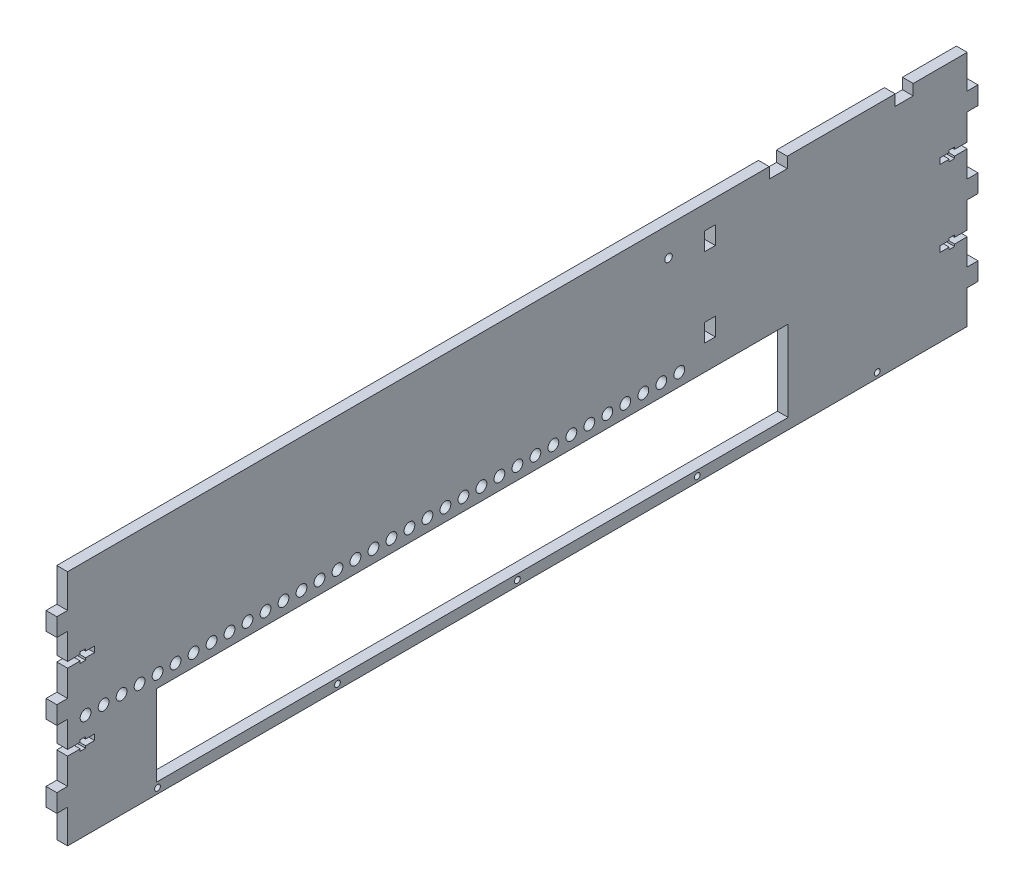
SolidWorks part; units mm, degrees
ref_plane "Front Plane" through (0, 0, 0) normal (0, 0, 1) x (1, 0, 0)
ref_plane "Top Plane" through (0, 0, 0) normal (0, 1, 0) x (1, 0, 0)
ref_plane "Right Plane" through (0, 0, 0) normal (1, 0, 0) x (0, 0, -1)
sketch "Sketch1" plane through (0, 0, 0) normal (1, 0, 0) x (0, 0, -1)
  line L1 (-250, -66) -> (250, -66)
  line L2 (-250, -66) -> (-250, 66)
  line L3 (-250, 66) -> (250, 66)
  line L4 (250, -66) -> (250, 66)
  line L5 (-250, -66) -> (250, 66) construction
  line L6 (-250, 66) -> (250, -66) construction
  point P0 (0, 0)
  dimension "D1" = 132
  dimension "D2" = 500
extrude "Boss-Extrude1" add sketch "Sketch1" along normal blind 6
sketch "Sketch4" plane through (0, 0, 250) normal (0, 0, 1) x (1, 0, 0)
  line L0 (0, 66) -> (0, -66) construction
  line L1 (0, 47.3321) -> (6, 47.3321)
  line L2 (0, 47.3321) -> (0, 37.3321)
  line L3 (0, 37.3321) -> (6, 37.3321)
  line L4 (6, 47.3321) -> (6, 37.3321)
  line L5 (6, 66) -> (6, -66) construction
  line L6 (0, 37.3321) -> (6, 37.3321) construction
  line L7 (0, -66) -> (0, 66) construction
  line L8 (6, 47.3321) -> (0, 47.3321) construction
  line L9 (0, -5) -> (6, -5) construction
  line L10 (0, -5) -> (6, -5)
  line L11 (0, -5) -> (0, 5)
  line L12 (0, 5) -> (6, 5)
  line L13 (6, -5) -> (6, 5)
  line L14 (6, -66) -> (6, 66) construction
  line L15 (6, 5) -> (0, 5) construction
  line L16 (6, -37.3321) -> (0, -37.3321) construction
  line L17 (0, -47.3321) -> (6, -47.3321)
  line L18 (0, -47.3321) -> (0, -37.3321)
  line L19 (0, -37.3321) -> (6, -37.3321)
  line L20 (6, -47.3321) -> (6, -37.3321)
  line L21 (0, -47.3321) -> (6, -47.3321) construction
extrude "Boss-Extrude2" add sketch "Sketch4" along normal blind 6
sketch "Sketch5" plane through (0, 0, 0) normal (-1, 0, 0) x (0, 0, 1)
  line L0 (250, 37.3321) -> (250, 5) construction
  line L1 (250, 5) -> (250, -5) construction
  line L2 (250, -5) -> (250, -37.3321) construction
  line L3 (250, 21.1661) -> (235, 21.1661) construction
  line L4 (240, -23.9661) -> (243, -18.3661) construction
  line L5 (250, 22.7661) -> (235, 22.7661)
  line L6 (240, -18.3661) -> (243, -23.9661) construction
  line L7 (250, 19.5661) -> (235, 19.5661)
  line L8 (250, -21.1661) -> (235, -21.1661) construction
  line L9 (250, 22.7661) -> (250, 19.5661)
  line L10 (235, 22.7661) -> (235, 19.5661)
  line L11 (243, -18.3661) -> (243, -23.9661)
  line L12 (240, -23.9661) -> (243, -23.9661)
  line L13 (250, 0) -> (222.8268, 0) construction
  line L14 (240, 18.3661) -> (243, 18.3661)
  line L15 (240, 18.3661) -> (240, 23.9661)
  line L16 (240, 23.9661) -> (243, 23.9661)
  line L17 (243, 18.3661) -> (243, 23.9661)
  line L18 (240, 18.3661) -> (243, 23.9661) construction
  line L19 (240, 23.9661) -> (243, 18.3661) construction
  line L20 (240, -18.3661) -> (240, -23.9661)
  line L21 (240, -18.3661) -> (243, -18.3661)
  line L22 (235, -22.7661) -> (235, -19.5661)
  line L23 (250, -22.7661) -> (250, -19.5661)
  line L24 (250, -19.5661) -> (235, -19.5661)
  line L25 (250, -22.7661) -> (235, -22.7661)
  point P20 (241.5, 21.1661)
  point P29 (241.5, -21.1661)
  dimension "D3" = 15
  dimension "D4" = 7
  dimension "D5" = 3
  dimension "D6" = 5.6
  dimension "D1" = 1.6
  dimension "D2" = 1.6
extrude "Cut-Extrude3" cut sketch "Sketch5" against normal up to next contours L17 L7 L9 L5 | L7 L17 L5 L15 | L5 L17 L16 L15 | L14 L17 L7 L15 | L7 L15 L5 L10 | L25 L23 L24 L11 | L25 L11 L24 L20 | L24 L11 L21 L20 | L11 L25 L20 L12 | L25 L20 L24 L22 region at (0, 21.1661, 246.5) region at (0, 21.1661, 241.5) region at (0, 23.3661, 241.5) region at (0, 21.1661, 237.5) region at (0, 18.9661, 241.5) region at (0, -18.9661, 241.5) region at (0, -21.1661, 246.5) region at (0, -21.1661, 241.5) region at (0, -23.3661, 241.5) region at (0, -21.1661, 237.5)
sketch "Sketch6" plane through (0, 0, -250) normal (0, 0, -1) x (-1, 0, 0)
  line L0 (0, 47.3321) -> (0, 37.3321) construction
  line L1 (0, 37.3321) -> (-6, 37.3321) construction
  line L2 (-6, 37.3321) -> (-6, 47.3321) construction
  line L3 (-6, 47.3321) -> (0, 47.3321) construction
  line L4 (0, 5) -> (0, -5) construction
  line L5 (0, -5) -> (-6, -5) construction
  line L6 (-6, -5) -> (-6, 5) construction
  line L7 (-6, 5) -> (0, 5) construction
  line L8 (0, -37.3321) -> (0, -47.3321) construction
  line L9 (0, -47.3321) -> (-6, -47.3321) construction
  line L10 (-6, -47.3321) -> (-6, -37.3321) construction
  line L11 (-6, -37.3321) -> (0, -37.3321) construction
  line L12 (0, 47.3321) -> (0, 37.3321)
  line L13 (0, 37.3321) -> (-6, 37.3321)
  line L14 (-6, 37.3321) -> (-6, 47.3321)
  line L15 (-6, 47.3321) -> (0, 47.3321)
  line L16 (0, 5) -> (0, -5)
  line L17 (0, -5) -> (-6, -5)
  line L18 (-6, -5) -> (-6, 5)
  line L19 (-6, 5) -> (0, 5)
  line L20 (0, -37.3321) -> (0, -47.3321)
  line L21 (0, -47.3321) -> (-6, -47.3321)
  line L22 (-6, -47.3321) -> (-6, -37.3321)
  line L23 (-6, -37.3321) -> (0, -37.3321)
extrude "Boss-Extrude3" add sketch "Sketch6" along normal blind 6
sketch "Sketch7" plane through (0, 0, 0) normal (-1, 0, 0) x (0, 0, 1)
  line L0 (0, 0) -> (0, -63.2146) construction
  line L1 (240, 22.7661) -> (240, 23.9661) construction
  line L2 (240, 22.7661) -> (235, 22.7661) construction
  line L3 (235, 22.7661) -> (235, 19.5661) construction
  line L4 (240, 19.5661) -> (235, 19.5661) construction
  line L5 (240, 18.3661) -> (240, 19.5661) construction
  line L6 (240, 18.3661) -> (243, 18.3661) construction
  line L7 (243, 18.3661) -> (243, 19.5661) construction
  line L8 (250, 19.5661) -> (243, 19.5661) construction
  line L9 (250, 22.7661) -> (243, 22.7661) construction
  line L10 (240, 23.9661) -> (243, 23.9661) construction
  line L11 (243, 22.7661) -> (243, 23.9661) construction
  line L12 (240, 22.7661) -> (235, 22.7661) construction
  line L13 (235, 22.7661) -> (235, 19.5661) construction
  line L14 (240, 19.5661) -> (235, 19.5661) construction
  line L15 (240, 18.3661) -> (240, 19.5661) construction
  line L16 (240, 18.3661) -> (243, 18.3661) construction
  line L17 (243, 18.3661) -> (243, 19.5661) construction
  line L18 (250, 19.5661) -> (243, 19.5661) construction
  line L19 (250, 22.7661) -> (243, 22.7661) construction
  line L20 (240, 23.9661) -> (243, 23.9661) construction
  line L21 (243, 22.7661) -> (243, 23.9661) construction
  line L22 (240, 22.7661) -> (240, 23.9661) construction
  line L23 (250, -19.5661) -> (243, -19.5661) construction
  line L24 (240, -18.3661) -> (243, -18.3661) construction
  line L25 (243, -18.3661) -> (243, -19.5661) construction
  line L26 (240, -18.3661) -> (240, -19.5661) construction
  line L27 (240, -19.5661) -> (235, -19.5661) construction
  line L28 (235, -22.7661) -> (235, -19.5661) construction
  line L29 (240, -22.7661) -> (235, -22.7661) construction
  line L30 (240, -22.7661) -> (240, -23.9661) construction
  line L31 (240, -23.9661) -> (243, -23.9661) construction
  line L32 (243, -22.7661) -> (243, -23.9661) construction
  line L33 (250, -22.7661) -> (243, -22.7661) construction
  line L34 (250, -19.5661) -> (243, -19.5661) construction
  line L35 (240, -18.3661) -> (243, -18.3661) construction
  line L36 (243, -18.3661) -> (243, -19.5661) construction
  line L37 (240, -18.3661) -> (240, -19.5661) construction
  line L38 (240, -19.5661) -> (235, -19.5661) construction
  line L39 (235, -22.7661) -> (235, -19.5661) construction
  line L40 (240, -22.7661) -> (235, -22.7661) construction
  line L41 (240, -22.7661) -> (240, -23.9661) construction
  line L42 (240, -23.9661) -> (243, -23.9661) construction
  line L43 (243, -22.7661) -> (243, -23.9661) construction
  line L44 (250, -22.7661) -> (243, -22.7661) construction
  line L45 (250, 22.7661) -> (250, 19.5661) construction
  line L46 (250, -19.5661) -> (250, -22.7661) construction
  line L47 (-250, -19.5661) -> (-250, -22.7661)
  line L48 (-250, 22.7661) -> (-250, 19.5661)
  line L49 (-250, -22.7661) -> (-243, -22.7661)
  line L50 (-243, -22.7661) -> (-243, -23.9661)
  line L51 (-240, -23.9661) -> (-243, -23.9661)
  line L52 (-240, -22.7661) -> (-240, -23.9661)
  line L53 (-240, -22.7661) -> (-235, -22.7661)
  line L54 (-235, -22.7661) -> (-235, -19.5661)
  line L55 (-240, -19.5661) -> (-235, -19.5661)
  line L56 (-240, -18.3661) -> (-240, -19.5661)
  line L57 (-243, -18.3661) -> (-243, -19.5661)
  line L58 (-240, -18.3661) -> (-243, -18.3661)
  line L59 (-250, -19.5661) -> (-243, -19.5661)
  line L60 (-240, 22.7661) -> (-240, 23.9661)
  line L61 (-243, 22.7661) -> (-243, 23.9661)
  line L62 (-240, 23.9661) -> (-243, 23.9661)
  line L63 (-250, 22.7661) -> (-243, 22.7661)
  line L64 (-250, 19.5661) -> (-243, 19.5661)
  line L65 (-243, 18.3661) -> (-243, 19.5661)
  line L66 (-240, 18.3661) -> (-243, 18.3661)
  line L67 (-240, 18.3661) -> (-240, 19.5661)
  line L68 (-240, 19.5661) -> (-235, 19.5661)
  line L69 (-235, 22.7661) -> (-235, 19.5661)
  line L70 (-240, 22.7661) -> (-235, 22.7661)
extrude "Cut-Extrude4" cut sketch "Sketch7" against normal up to next
sketch "Sketch8" plane through (0, 0, 0) normal (-1, 0, 0) x (0, 0, 1)
  line L0 (200, -15.55) -> (-150, -15.55) construction
  line L1 (200, -15.55) -> (-150, -15.55) construction
  line L2 (200, -15.55) -> (200, -60) construction
  line L3 (200, -15.55) -> (200, -60) construction
  line L186 (-150, -15.55) -> (-150, -60) construction
  line L187 (-150, -60) -> (200, -60) construction
  line L188 (200.5, -15.05) -> (200.5, -60)
  line L189 (200.5, -15.05) -> (-150.5, -15.05)
  line L190 (-150.5, -15.05) -> (-150.5, -60)
  line L191 (-150.5, -60) -> (200.5, -60)
  dimension "D1" = 0.5
extrude "Cut-Extrude5" cut sketch "Sketch8" against normal up to next
sketch "Sketch10" plane through (6, 0, 0) normal (1, 0, 0) x (0, 0, -1)
  line L0 (0, 0) -> (0, -66) construction
  line L1 (-250, -66) -> (250, -66) construction
  line L2 (0, -63) -> (250, -63) construction
  line L3 (250, -66) -> (250, -47.3321) construction
  circle A0 centre (0, -63) radius 1.6
  circle A1 centre (100, -63) radius 1.6
  circle A2 centre (200, -63) radius 1.6
  circle A3 centre (-100, -63) radius 1.6
  circle A4 centre (-200, -63) radius 1.6
  dimension "D2" = 3.2
  dimension "D1" = 3
  dimension "D3" = 100
  dimension "D4" = 100
extrude "Cut-Extrude7" cut sketch "Sketch10" against normal up to next
sketch "Sketch11" plane through (6, 0, 0) normal (1, 0, 0) x (0, 0, -1)
  line L0 (110, 43) -> (110, 53) construction
  line L1 (110, 53) -> (104, 53) construction
  line L2 (104, 53) -> (104, 43) construction
  line L3 (104, 43) -> (110, 43) construction
  line L4 (110, -1) -> (110, 9) construction
  line L5 (110, 9) -> (104, 9) construction
  line L6 (104, 9) -> (104, -1) construction
  line L7 (104, -1) -> (110, -1) construction
  line L8 (110, 43) -> (110, 53)
  line L9 (110, 53) -> (104, 53)
  line L10 (104, 53) -> (104, 43)
  line L11 (104, 43) -> (110, 43)
  line L12 (110, -1) -> (110, 9)
  line L13 (110, 9) -> (104, 9)
  line L14 (104, 9) -> (104, -1)
  line L15 (104, -1) -> (110, -1)
extrude "Cut-Extrude8" cut sketch "Sketch11" against normal up to next
sketch "Sketch12" plane through (0, 0, 0) normal (-1, 0, 0) x (0, 0, 1)
  line L0 (-104, 53) -> (-104, 43) construction
  line L1 (-250, 66) -> (250, 66) construction
  circle A0 centre (-84, 50) radius 2.1
  dimension "D1" = 20
  dimension "D3" = 4.2
  dimension "D2" = 16
extrude "Cut-Extrude9" cut sketch "Sketch12" against normal up to next
sketch "Sketch13" plane through (0, 66, 0) normal (0, 1, 0) x (1, 0, 0)
  line L0 (6, 250) -> (6, -250) construction
  line L1 (0, 210) -> (6, 210)
  line L2 (0, 210) -> (0, 220)
  line L3 (0, 220) -> (6, 220)
  line L4 (6, 210) -> (6, 220)
  line L5 (0, 210) -> (6, 220) construction
  line L6 (0, 220) -> (6, 210) construction
  line L7 (6, 220) -> (0, 220) construction
  line L8 (6, 150) -> (0, 150) construction
  line L9 (0, 140) -> (6, 140)
  line L10 (0, 140) -> (0, 150)
  line L11 (0, 150) -> (6, 150)
  line L12 (6, 140) -> (6, 150)
  line L13 (0, 140) -> (6, 150) construction
  line L14 (0, 150) -> (6, 140) construction
  point P0 (3, 215)
  point P10 (3, 145)
extrude "Cut-Extrude10" cut sketch "Sketch13" against normal blind 6
sketch "Sketch14" plane through (0, 0, 0) normal (-1, 0, 0) x (0, 0, 1)
  circle A0 centre (240, -8) radius 3 construction
  circle A1 centre (240, -8) radius 3
  circle A2 centre (230, -8) radius 3
  circle A3 centre (220, -8) radius 3
  circle A4 centre (210, -8) radius 3
  circle A5 centre (200, -8) radius 3
  circle A6 centre (190, -8) radius 3
  circle A7 centre (180, -8) radius 3
  circle A8 centre (170, -8) radius 3
  circle A9 centre (160, -8) radius 3
  circle A10 centre (150, -8) radius 3
  circle A11 centre (140, -8) radius 3
  circle A12 centre (130, -8) radius 3
  circle A13 centre (120, -8) radius 3
  circle A14 centre (110, -8) radius 3
  circle A15 centre (100, -8) radius 3
  circle A16 centre (90, -8) radius 3
  circle A17 centre (80, -8) radius 3
  circle A18 centre (70, -8) radius 3
  circle A19 centre (60, -8) radius 3
  circle A20 centre (50, -8) radius 3
  circle A21 centre (40, -8) radius 3
  circle A22 centre (30, -8) radius 3
  circle A23 centre (20, -8) radius 3
  circle A24 centre (10, -8) radius 3
  circle A25 centre (0, -8) radius 3
  circle A26 centre (-10, -8) radius 3
  circle A27 centre (-20, -8) radius 3
  circle A28 centre (-30, -8) radius 3
  circle A29 centre (-40, -8) radius 3
  circle A30 centre (-50, -8) radius 3
  circle A31 centre (-60, -8) radius 3
  circle A32 centre (-70, -8) radius 3
  circle A33 centre (-80, -8) radius 3
  circle A34 centre (-90, -8) radius 3
  dimension "D1" = 34
extrude "Cut-Extrude11" cut sketch "Sketch14" against normal up to next (6 mm away)
